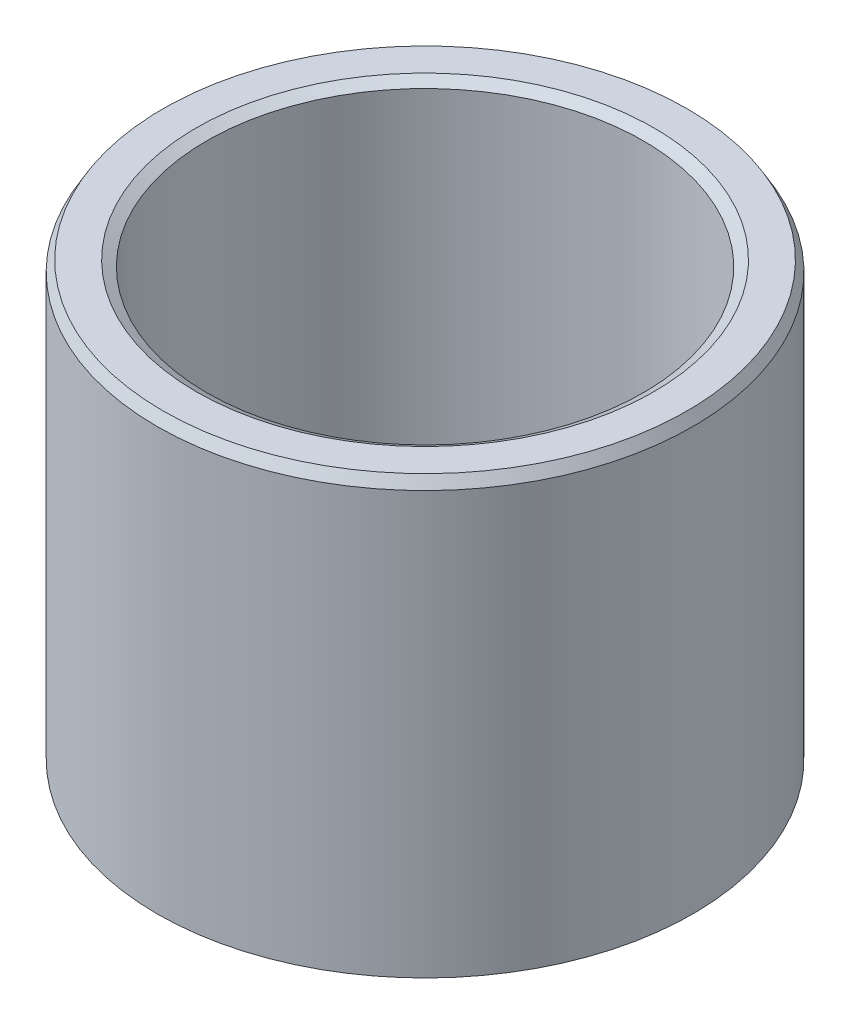
SolidWorks part; units mm, degrees
ref_plane "Front Plane" through (0, 0, 0) normal (0, 0, 1) x (1, 0, 0)
ref_plane "Top Plane" through (0, 0, 0) normal (0, 1, 0) x (1, 0, 0)
ref_plane "Right Plane" through (0, 0, 0) normal (1, 0, 0) x (0, 0, -1)
sketch "Sketch1" plane through (0, 0, 0) normal (0, 1, 0) x (1, 0, 0)
  circle A0 centre (0, 0) radius 32.5
  dimension "SLEEVE_OD" = 65
extrude "Boss-Extrude1" add sketch "Sketch1" along normal blind 53.2001
sketch "Sketch2" plane through (0, 0, 0) normal (0, 1, 0) x (1, 0, 0)
  circle A0 centre (0, 0) radius 26.4798
  dimension "BORE_D" = 52.9595
extrude "Cut-Extrude1" cut sketch "Sketch2" along normal through all
chamfer "Chamfer1" distance 1.2649 angle 30 4 edges at (0, 53.2001, 26.4798) (0, 0, 26.4798) (0, 0, 32.5) (0, 53.2001, 32.5) first distance on face at (0, 53.2001, 26.4798) first distance on face at (0, 0, 26.4798) first distance on face at (0, 53.2001, 32.5)
